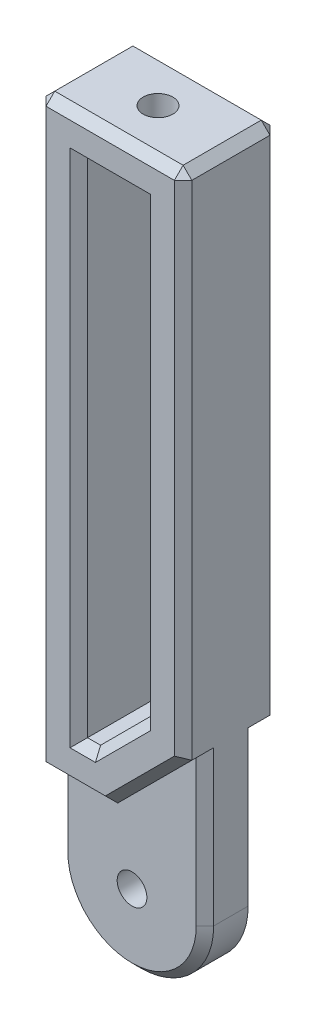
SolidWorks part; units mm, degrees
ref_plane "Front Plane" through (0, 0, 0) normal (0, 0, 1) x (1, 0, 0)
ref_plane "Top Plane" through (0, 0, 0) normal (0, 1, 0) x (1, 0, 0)
ref_plane "Right Plane" through (0, 0, 0) normal (1, 0, 0) x (0, 0, -1)
sketch "Sketch1" plane through (0, 0, 0) normal (0, 0, 1) x (1, 0, 0)
  line L2 (-8.35, 0) -> (-8.35, 76.2)
  line L3 (-8.35, 76.2) -> (8.35, 76.2)
  line L4 (8.35, 0) -> (8.35, 76.2)
  arc A1 (-8.35, 0) -> (8.35, 0) centre (0, 0) ccw
  dimension "D2" = 8.35
  dimension "D1" = 76.2
extrude "Boss-Extrude1" add sketch "Sketch1" along normal mid plane 5.95
sketch "Sketch4" plane through (0, 0, 2.975) normal (0, 0, 1) x (1, 0, 0)
  line L0 (-8.35, 76.2) -> (-8.35, 9.2)
  line L1 (-8.35, 76.2) -> (-8.35, 0) construction
  line L2 (-8.35, 9.2) -> (-0.1353, 9.2)
  line L3 (-0.1353, 9.2) -> (8.35, 17.6853)
  line L4 (8.35, 0) -> (8.35, 76.2) construction
  line L5 (8.35, 17.6853) -> (8.35, 76.2)
  line L6 (8.35, 76.2) -> (-8.35, 76.2)
  line L7 (-0.1353, 9.2) -> (8.35, 9.2) construction
  dimension "D1" = 45
  dimension "D2" = 67
  dimension "D3" = 12
extrude "Boss-Extrude2" add sketch "Sketch4" along normal blind 2.5
extrude "Boss-Extrude3" add sketch "Sketch4<2>" against normal blind 2.5 from surface starting at face at (0, 36.0125, -2.975)
sketch "Sketch4<2>" plane through (0, 0, 2.975) normal (0, 0, 1) x (1, 0, 0) same geometry as "Sketch4"
sketch "Sketch5" plane through (0, 0, 5.475) normal (0, 0, 1) x (1, 0, 0)
  line L5 (-3.6, 13.95) -> (-2.1028, 13.95)
  line L8 (-3.6, 13.95) -> (-2.1028, 13.95)
  line L10 (3.6, 71.45) -> (-3.6, 71.45)
  line L11 (-3.6, 71.45) -> (-3.6, 13.95)
  line L13 (-2.1028, 13.95) -> (3.6, 19.6528)
  line L14 (3.6, 19.6528) -> (3.6, 71.45)
  line L15 (3.6, 71.45) -> (-3.6, 71.45)
  line L16 (-3.6, 71.45) -> (-3.6, 13.95)
  line L18 (-2.1028, 13.95) -> (3.6, 19.6528)
  line L19 (3.6, 19.6528) -> (3.6, 71.45)
  dimension "D1" = 4.75
extrude "Cut-Extrude3" cut sketch "Sketch5" against normal through all
sketch "Sketch6" plane through (0, 71.45, 0) normal (0, -1, 0) x (1, 0, 0)
  line L0 (8.35, -5.475) -> (-8.35, -5.475) construction
  line L1 (-8.35, 5.475) -> (-8.35, -5.475) construction
  circle A0 centre (0, 0) radius 1.7
  point P4 (0, -5.475)
  point P7 (-8.35, 0)
  dimension "D1" = 3.4
extrude "Cut-Extrude4" cut sketch "Sketch6" against normal through all
sketch "Sketch7" plane through (0, 0, 2.975) normal (0, 0, 1) x (1, 0, 0)
  circle A0 centre (0, 0) radius 1.7
  arc A1 (-8.35, 0) -> (8.35, 0) centre (0, 0) ccw construction
  dimension "D1" = 3.4
extrude "Cut-Extrude5" cut sketch "Sketch7" against normal through all
chamfer "Chamfer1" distance 1 angle 45 28 edges at (8.35, 46.9426, -5.475) (0, 76.2, -5.475) (-8.35, 42.7, -5.475) (-4.2426, 9.2, -5.475) (4.1074, 13.4426, -5.475) (-2.8514, 13.95, -5.475) (-3.6, 42.7, -5.475) (0, 71.45, -5.475) (3.6, 45.5514, -5.475) (0.7486, 16.8014, -5.475) (0, 76.2, 5.475) (8.35, 46.9426, 5.475) (4.1074, 13.4426, 5.475) (-4.2426, 9.2, 5.475) (-8.35, 42.7, 5.475) (-2.8514, 13.95, 5.475) (0.7486, 16.8014, 5.475) (3.6, 45.5514, 5.475) (0, 71.45, 5.475) (-3.6, 42.7, 5.475) (-8.35, 4.6, -2.975) (0, -8.35, -2.975) (8.35, 8.8426, -2.975) (-8.35, 4.6, 2.975) (0, -8.35, 2.975) (8.35, 8.8426, 2.975) (-8.35, 76.2, 0) (8.35, 76.2, 0)
